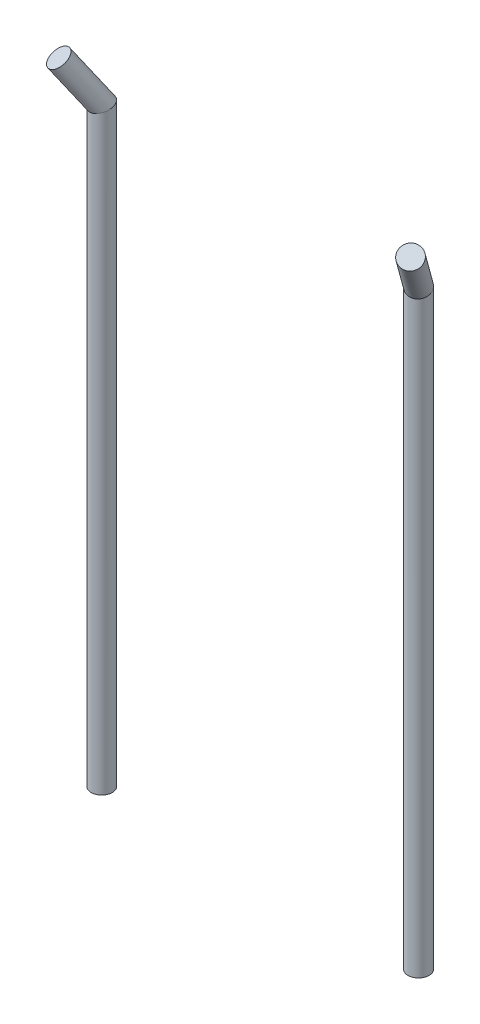
SolidWorks part; units mm, degrees
ref_plane "前视基准面" through (0, 0, 0) normal (0, 0, 1) x (1, 0, 0)
ref_plane "上视基准面" through (0, 0, 0) normal (0, 1, 0) x (1, 0, 0)
ref_plane "右视基准面" through (0, 0, 0) normal (1, 0, 0) x (0, 0, -1)
sketch "草图1" plane through (0, 0, 0) normal (0, 0, 1) x (1, 0, 0)
  line L0 (0, 0) -> (0, 280) construction
  line L1 (150, 0) -> (150, 280) construction
  dimension "D1" = 280
  dimension "D2" = 150
ref_axis "基准轴1" through (0, 280, 0) along (1, 0, 0)
ref_plane "基准面1" through (0, 70, -121.2436) normal (0, -0.5, 0.866) x (1, 0, 0)
sketch "草图2" plane through (0, 70, -121.2436) normal (0, -0.5, 0.866) x (1, 0, 0)
  line L0 (-7.4169, 262.8648) -> (-37.4996, 345.5164)
  line L1 (-4.6104, 392.4871) -> (154.6104, 392.4871)
  line L2 (187.4996, 345.5164) -> (157.4169, 262.8648)
  line L3 (0, 242.4871) -> (150, 242.4871) construction
  line L4 (-37.4996, 262.8648) -> (191.4707, 262.8648) construction
  line L5 (-7.4169, 262.8648) -> (0, 242.4871) construction
  line L6 (157.4169, 262.8648) -> (150, 242.4871) construction
  arc A0 (154.6104, 392.4871) -> (187.4996, 345.5164) centre (154.6104, 357.4871) cw
  arc A1 (-37.4996, 345.5164) -> (-4.6104, 392.4871) centre (-4.6104, 357.4871) cw
  dimension "D4" = 35
  dimension "D1" = 110
  dimension "D2" = 110
  dimension "D3" = 150
ref_plane "基准面2" through (98.0458, 0, -71.3715) normal (0.8085, 0, -0.5885) x (-0.5885, 0, -0.8085)
ref_plane "基准面3" through (0, 0, 0) normal (0.8085, 0, 0.5885) x (0.5885, 0, -0.8085)
sketch "草图90" plane through (98.0458, 0, -71.3715) normal (0.8085, 0, -0.5885) x (-0.5885, 0, -0.8085)
  line L0 (-105.5216, 304.1457) -> (-88.2787, 280)
  line L1 (-151.9967, 369.226) -> (-100.8812, 297.6476) construction
  line L2 (-88.2787, 280) -> (-88.2787, 0)
sketch "草图91" plane through (0, 0, 0) normal (0.8085, 0, 0.5885) x (0.5885, 0, -0.8085)
  line L0 (0, 0) -> (0, 280)
  line L1 (0, 280) -> (-14.5734, 300.4076)
  line L2 (-12.6025, 297.6476) -> (-63.718, 369.226) construction
sweep "扫描4" add path "草图90" circular profile diameter 10 parameters "D3"=10
sweep "扫描5" add path "草图91" circular profile diameter 10 parameters "D3"=10
